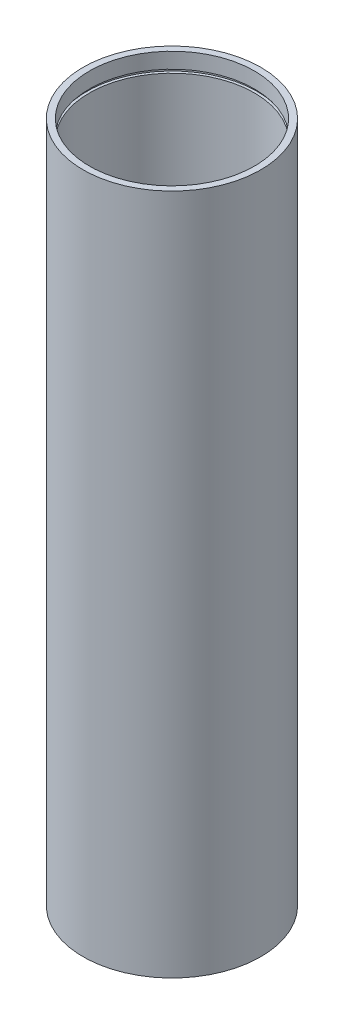
SolidWorks part; units mm, degrees
material "1060 Alloy"
ref_plane "Front Plane" through (0, 0, 0) normal (0, 0, 1) x (1, 0, 0)
ref_plane "Top Plane" through (0, 0, 0) normal (0, 1, 0) x (1, 0, 0)
ref_plane "Right Plane" through (0, 0, 0) normal (1, 0, 0) x (0, 0, -1)
sketch "Sketch2" plane through (0, 0, 0) normal (0, 0, 1) x (1, 0, 0)
  line L0 (0, 0) -> (0, 365.76) construction
  line L1 (41.275, 11.2522) -> (42.5958, 11.2522)
  line L2 (42.5958, 11.2522) -> (42.5958, 9.525)
  line L3 (41.275, 0) -> (44.45, 0)
  line L4 (41.275, 340.9442) -> (41.275, 333.1464)
  line L5 (41.275, 340.9442) -> (44.45, 340.9442)
  line L6 (44.45, 0) -> (44.45, 340.9442)
  line L7 (42.5958, 9.525) -> (41.275, 9.525)
  line L8 (41.275, 331.4192) -> (42.5958, 331.4192)
  line L9 (42.5958, 331.4192) -> (42.5958, 333.1464)
  line L10 (42.5958, 333.1464) -> (41.275, 333.1464)
  line L11 (41.275, 331.4192) -> (41.275, 11.2522)
  line L12 (41.275, 11.2522) -> (41.2565, 11.2265)
  line L13 (41.275, 9.525) -> (41.275, 0)
  line L14 (0, -55) -> (0, 55) construction
  point P18 (0, 0)
  point P19 (0, 0)
  dimension "D3" = 3.175
  dimension "D4" = 340.9442
  dimension "D5" = 9.525
  dimension "D6" = 1.7272
  dimension "D7" = 1.3208
  dimension "D8" = 9.525
  dimension "D9" = 1.3208
  dimension "D10" = 1.7272
revolve "Revolve1" add sketch "Sketch2" angle 360 about L0 region at (42.8664, 170.4684, 0)
